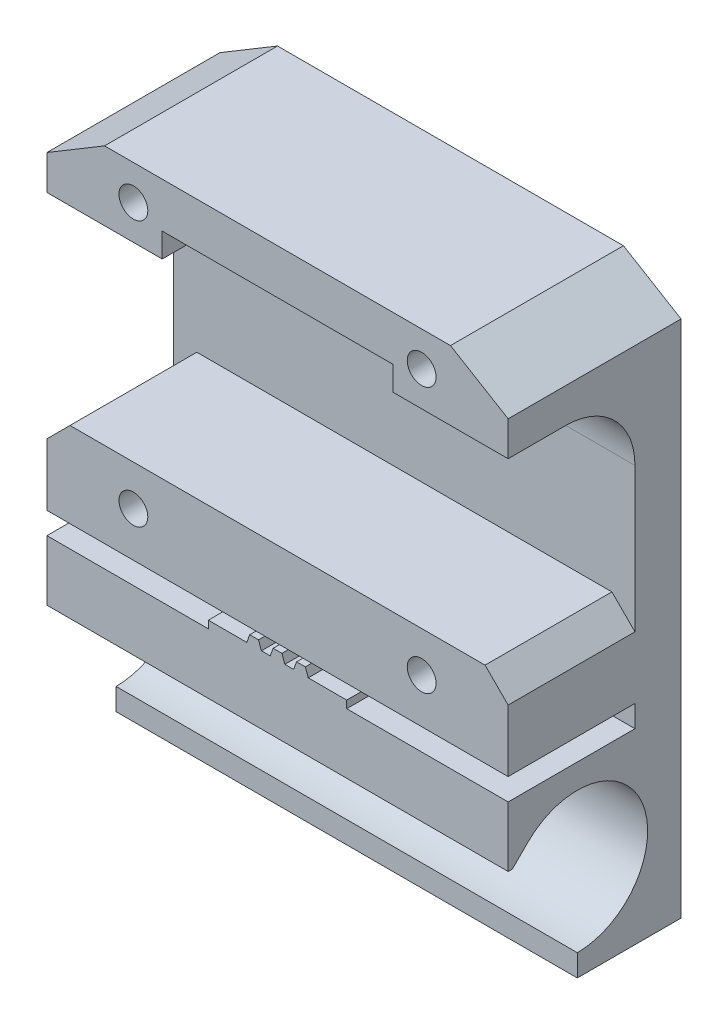
SolidWorks part; units mm, degrees
material "ABS"
ref_plane "Front Plane" through (0, 0, 0) normal (0, 0, 1) x (1, 0, 0)
ref_plane "Top Plane" through (0, 0, 0) normal (0, 1, 0) x (1, 0, 0)
ref_plane "Right Plane" through (0, 0, 0) normal (1, 0, 0) x (0, 0, -1)
sketch "Sketch1" plane through (0, 0, 0) normal (0, 0, 1) x (1, 0, 0)
  line L1 (-23.7591, 22) -> (52.715, 22) construction
  line L2 (0, -10) -> (0, 38)
  line L3 (0, 38) -> (40, 38)
  line L4 (40, -10) -> (40, 38)
  line L6 (0, -10) -> (40, -10)
  point P2 (0, 22)
  point P9 (40, 22)
  point P10 (0, 22)
  point P13 (40, 22)
  dimension "D1" = 48
  dimension "D2" = 40
extrude "Boss-Extrude1" add sketch "Sketch1" along normal blind 4
ref_plane "Plane2" through (0, 13, 0) normal (0, -1, 0) x (1, 0, 0)
sketch "Sketch2" plane through (0, 0, 4) normal (0, 0, 1) x (1, 0, 0)
  line L0 (20, 38) -> (20, 20.7808) construction
  line L1 (15.9, 33) -> (24.1, 33)
  line L2 (15.9, 33) -> (15.9, 23)
  line L3 (15.9, 23) -> (24.1, 23)
  line L4 (24.1, 33) -> (24.1, 23)
  line L5 (40, 38) -> (0, 38) construction
  line L6 (-2.2, 13) -> (2.2, 13) construction
  line L9 (2, 3) -> (10.2, 3)
  line L10 (2, 3) -> (2, -7)
  line L11 (2, -7) -> (10.2, -7)
  line L12 (10.2, 3) -> (10.2, -7)
  line L14 (29.8, 3) -> (29.8, -7)
  line L15 (38, -7) -> (29.8, -7)
  line L16 (38, 3) -> (38, -7)
  line L17 (38, 3) -> (29.8, 3)
  line L18 (15.9, 28) -> (24.1, 28) construction
  line L19 (2, -2) -> (38, -2) construction
  dimension "D1" = 8.2
  dimension "D2" = 10
  dimension "D3" = 20
  dimension "D4" = 4.1
  dimension "D5" = 30
  dimension "D6" = 2
extrude "Cut-Extrude1" [suppressed] cut sketch "Sketch2" against normal blind 1
sketch "Sketch3" [suppressed] plane through (0, 0, 3) normal (0, 0, 1) x (1, 0, 0)
  line L0 (15.9, 33) -> (15.9, 23) construction
  line L1 (15.9, 32.1) -> (24.1, 32.1)
  line L2 (15.9, 32.1) -> (15.9, 23.9)
  line L3 (15.9, 23.9) -> (24.1, 23.9)
  line L4 (24.1, 32.1) -> (24.1, 23.9)
  line L5 (24.1, 23) -> (24.1, 33) construction
  line L6 (24.1, 33) -> (15.9, 33) construction
  line L7 (15.9, 23) -> (24.1, 23) construction
  line L8 (2, 3) -> (2, -7) construction
  line L9 (2, 2.1) -> (10.2, 2.1)
  line L10 (2, 2.1) -> (2, -6.1)
  line L11 (2, -6.1) -> (10.2, -6.1)
  line L12 (10.2, 2.1) -> (10.2, -6.1)
  line L13 (10.2, -7) -> (10.2, 3) construction
  line L14 (29.8, 3) -> (29.8, -7) construction
  line L15 (29.8, 2.1) -> (38, 2.1)
  line L16 (29.8, 2.1) -> (29.8, -6.1)
  line L17 (29.8, -6.1) -> (38, -6.1)
  line L18 (38, 2.1) -> (38, -6.1)
  line L19 (38, -7) -> (38, 3) construction
  line L20 (2, -7) -> (10.2, -7) construction
  dimension "D1" = 0.9
  dimension "D2" = 0.9
  dimension "D3" = 0.9
extrude "Cut-Extrude2" [suppressed] cut sketch "Sketch3" against normal blind 4
chamfer "Chamfer1" [suppressed] distance 1 angle 45
sketch "Sketch4" [suppressed] plane through (0, 0, 3) normal (0, 0, 1) x (1, 0, 0)
  line L0 (24.1, 35.1) -> (15.9, 35.1) construction
  line L1 (15.9, 35.1) -> (15.9, 26.9) construction
  line L2 (2, 1) -> (38, 1) construction
  line L3 (2, 5.1) -> (2, -3.1) construction
  line L4 (38, -7) -> (38, 3) construction
  line L5 (6.1, 2.1) -> (6.1, -3.1) construction
  line L7 (2, -3.1) -> (10.2, -3.1) construction
  line L8 (33.9, 2.1) -> (33.9, -3.1) construction
  line L10 (29.8, -3.1) -> (38, -3.1) construction
  line L12 (10.2, 2.1) -> (2, 2.1) construction
  line L13 (38, 2.1) -> (29.8, 2.1) construction
  circle A0 centre (20, 31) radius 1.65
  circle A1 centre (6.1, 1) radius 1.65
  circle A2 centre (33.9, 1) radius 1.65
  dimension "D1" = 3.3
  dimension "D2" = 4.1
  dimension "D3" = 4.1
extrude "Cut-Extrude3" [suppressed] cut sketch "Sketch4" against normal through all
ref_plane "Plane1" through (20, 0, 0) normal (1, 0, 0) x (0, 0, -1)
sketch "Sketch5" plane through (0, 0, 4) normal (0, 0, 1) x (1, 0, 0)
  line L0 (-5.9966, 13) -> (42.103, 13) construction
  line L1 (40, 8.125) -> (0, 8.125)
  line L2 (40, 6.225) -> (40, 1)
  line L3 (14, 6.875) -> (17.3332, 6.875)
  line L4 (20, 10.5) -> (20, 15.5) construction
  line L5 (40, 15.5) -> (40, 8.125)
  line L6 (20, -2.2) -> (20, 2.2) construction
  line L7 (0, -10) -> (40, -10) construction
  line L8 (0, 1) -> (40, 1)
  line L9 (20.38, 7.575) -> (19.62, 7.575)
  line L10 (19.62, 7.575) -> (19.3652, 6.875)
  line L11 (18.6028, 6.875) -> (18.348, 7.575)
  line L12 (18.348, 7.575) -> (17.588, 7.575)
  line L13 (17.588, 7.575) -> (17.3332, 6.875)
  line L14 (-2.2, 13) -> (2.2, 13) construction
  line L15 (18.6028, 6.875) -> (19.3652, 6.875)
  line L16 (21.3972, 6.875) -> (20.6348, 6.875)
  line L17 (22.412, 7.575) -> (22.6668, 6.875)
  line L18 (21.652, 7.575) -> (22.412, 7.575)
  line L19 (21.3972, 6.875) -> (21.652, 7.575)
  line L20 (20.38, 7.575) -> (20.6348, 6.875)
  line L21 (26, 6.875) -> (22.6668, 6.875)
  line L22 (0, 6.225) -> (14, 6.225)
  line L23 (14, 6.225) -> (14, 6.875)
  line L24 (26, 6.875) -> (26, 6.225)
  line L25 (26, 6.225) -> (40, 6.225)
  line L29 (0, -10) -> (40, -10)
  line L34 (0, -10) -> (0, -5)
  line L40 (40, -10) -> (40, 38) construction
  line L42 (40, 15.5) -> (0, 15.5)
  line L43 (0, 15.5) -> (0, 8.125)
  line L46 (0, 38) -> (0, -10) construction
  line L47 (0, 32) -> (40, 32)
  line L48 (0, 32) -> (0, 38)
  line L49 (0, -5) -> (40, -5)
  line L50 (40, 32) -> (40, 38)
  line L51 (0, 38) -> (40, 38)
  line L52 (40, -10) -> (40, -5)
  line L53 (40, 38) -> (0, 38) construction
  line L62 (0, 6.225) -> (0, 1)
  point P29 (20, 7.575)
  dimension "D2" = 0.38
  dimension "D3" = 0.55
  dimension "D4" = 40
  dimension "D5" = 0.76
  dimension "D7" = 1.25
  dimension "D9" = 5
  dimension "D10" = 2.032
  dimension "D11" = 1.9
  dimension "D19" = 2.5
  dimension "D8" = 4.875
  dimension "D12" = 12
  dimension "D13" = 12
  dimension "D6" = 19
extrude "Boss-Extrude2" add sketch "Sketch5" along normal blind 11 and the other way up to surface (4 mm away) other way up to face at (20, 14, 0)
fillet "Fillet1" radius 6 2 edges at (20, 32, 4) (20, 1, 4) tangent propagation no
sketch "Sketch6" plane through (0, 0, 15) normal (0, 0, 1) x (1, 0, 0)
  line L0 (7.5, 41.1026) -> (7.5, 12.7733) construction
  line L2 (20, 38) -> (20, 13.7162) construction
  line L3 (20, -2.2) -> (20, 2.2) construction
  line L4 (-2.2, 13) -> (2.2, 13) construction
  line L6 (40, 38) -> (0, 38) construction
  circle A0 centre (7.5, 35) radius 1.25
  circle A1 centre (7.5, 12) radius 1.25
  circle A2 centre (32.5, 35) radius 1.25
  circle A3 centre (32.5, 12) radius 1.25
  dimension "D1" = 2.5
  dimension "D2" = 23
  dimension "D3" = 22
  dimension "D4" = 12.5
extrude "Cut-Extrude4" cut sketch "Sketch6" against normal through all
chamfer "Chamfer2" distance 2 angle 45 2 edges at (0, 15.5, 9.5) (40, 15.5, 9.5)
sketch "Sketch7" plane through (0, 0, 4) normal (0, 0, 1) x (1, 0, 0)
  line L0 (0, 26) -> (0, 13.5) construction
  line L1 (0, 22) -> (40, 22)
  line L2 (0, 22) -> (0, 15.5)
  line L3 (0, 15.5) -> (40, 15.5)
  line L4 (40, 22) -> (40, 15.5)
  line L7 (38, 15.5) -> (2, 15.5) construction
  line L8 (-2.2, 13) -> (2.2, 13) construction
  dimension "D1" = 9
extrude "Cut-Extrude5" [suppressed] cut sketch "Sketch7" against normal blind 3
fillet "Fillet2" [suppressed] radius 3
chamfer "Chamfer3" [suppressed] distance 3 distance2 1
chamfer "Chamfer4" [suppressed] distance 3 distance2 0.5
sketch "Sketch8" plane through (20, 0, 0) normal (1, 0, 0) x (0, 0, -1)
  line L0 (-9, 28) -> (-9, -2) construction
  line L1 (-15, 38) -> (0, 38) construction
  line L3 (-4, 6.225) -> (-4, 8.125) construction
  line L4 (-9, 34.1) -> (-18.8209, 34.1)
  line L5 (-18.8209, 34.1) -> (-18.8209, 21.9)
  line L6 (-18.8209, 21.9) -> (-9, 21.9)
  arc A0 (-9, 21.9) -> (-9, 34.1) centre (-9, 28) ccw
  dimension "D1" = 30
  dimension "D3" = 10
  dimension "D4" = 5
extrude "Cut-Extrude6" cut sketch "Sketch8" against normal blind 10 and the other way blind 10
sketch "Sketch12" plane through (0, 38, 0) normal (0, 1, 0) x (1, 0, 0)
  line L1 (10, -4) -> (0, -4) construction
  circle A0 centre (15.4, -9) radius 3
  dimension "D3" = 6
  dimension "D1" = 5
  dimension "D2" = 15.4
extrude "Cut-Extrude8" [suppressed] cut sketch "Sketch12" against normal up to surface (22.5 mm away) up to face at (20, 15.5, 9.5)
sketch "Sketch13" [suppressed] plane through (0, 15.5, 0) normal (0, 1, 0) x (1, 0, 0)
  circle A0 centre (15.4, -9) radius 1.5
  circle A1 centre (15.4, -9) radius 3 construction
  dimension "D1" = 3
extrude "Cut-Extrude10" [suppressed] cut sketch "Sketch13" against normal offset from surface (10.275 mm away) 1 up to face at (15.6666, 6.875, 9.5) offset beyond the face yes
sketch "Sketch9" [suppressed] plane through (0, 13, 0) normal (0, -1, 0) x (1, 0, 0)
  line L0 (12.5, 16.8153) -> (18.3, 16.8153)
  line L1 (15.4, 5.6514) -> (18.3, 7.3257)
  line L2 (18.3, 7.3257) -> (18.3, 16.8153)
  line L5 (12.5, 16.8153) -> (12.5, 7.3257)
  line L6 (12.5, 7.3257) -> (15.4, 5.6514)
  line L8 (13.9872, 11.5329) -> (12.1308, 10.4612) [skipped]
  line L9 (16.8128, 11.5329) -> (14.9564, 12.6047) [skipped]
  circle A0 centre (15.4, 9) radius 2.9 construction
  arc A1 (18.4, 9) -> (12.4, 9) centre (15.4, 9) ccw construction
  dimension "D1" = 5.8
extrude "Cut-Extrude7" [suppressed] cut sketch "Sketch9" against normal blind 1.25 and the other way blind 1.25
chamfer "Chamfer5" distance 5 distance2 3 1 edges at (0, 38, 7.5) first distance on face at (20, 38, 7.5)
chamfer "Chamfer6" distance 3 distance2 5 1 edges at (40, 38, 7.5) first distance on face at (40, 11.5403, 9.2656)
sketch "Sketch14" plane through (0, 0, 0) normal (0, 0, -1) x (-1, 0, 0)
  line L1 (0, 35) -> (0, -10) construction
  line L4 (-18, 28.5) -> (-5, 28.5) construction
  line L6 (-35, 38) -> (-5, 38) construction
  circle A4 centre (-5, 28.5) radius 1.35
  circle A5 centre (-18, 28.5) radius 1.35
  dimension "D11" = 5
  dimension "D14" = 2.7
  dimension "D10" = 9.5
  dimension "D12" = 13
extrude "Cut-Extrude11" [suppressed] cut sketch "Sketch14" against normal blind 10
sketch "Sketch15" plane through (20, 0, 0) normal (1, 0, 0) x (0, 0, -1)
  line L0 (-9, 28) -> (-9, -2) construction
  line L1 (-15, 38) -> (0, 38) construction
  line L2 (-4, 13.5) -> (-4, 26) construction
  circle A0 centre (-9, -2) radius 3.5
  circle A1 centre (-9, 28) radius 3.5 construction
  dimension "D1" = 7
  dimension "D3" = 10
  dimension "D2" = 30
  dimension "D4" = 5
extrude "Cut-Extrude12" cut sketch "Sketch15" against normal through all and the other way through all
sketch "Sketch16" plane through (20, 0, -20) normal (-1, 0, 0) x (0, 0, 1)
  line L0 (29, 28) -> (29, -2) construction
  line L1 (29, -10.4726) -> (38.8209, -10.4726)
  line L2 (29, -8.1) -> (29, -10.4726)
  line L3 (38.8209, -3.1942) -> (33.3134, 2.3134)
  line L7 (38.8209, -10.4726) -> (38.8209, -3.1942)
  arc A1 (29, 34.1) -> (24, 24.5057) centre (29, 28) ccw construction
  arc A2 (29, -8.1) -> (33.3134, 2.3134) centre (29, -2) cw
  dimension "D1" = 30
extrude "Cut-Extrude13" cut sketch "Sketch16" against normal through all and the other way through all
